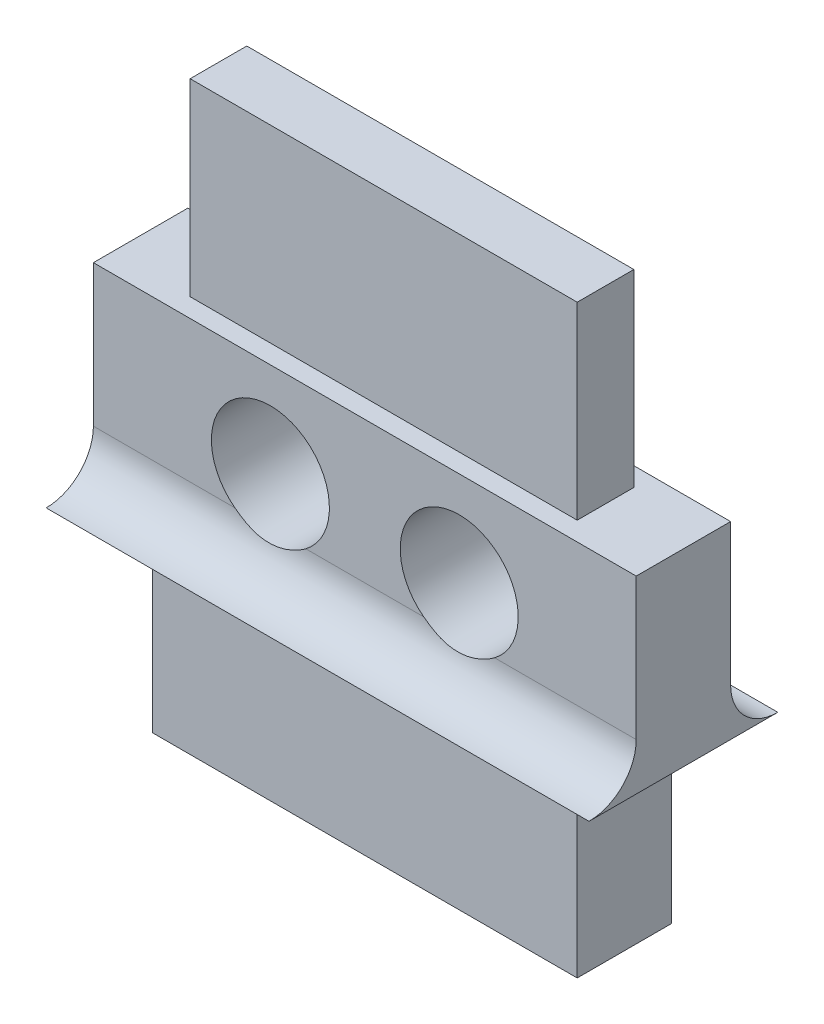
SolidWorks part; units mm, degrees
ref_plane "Front Plane" through (0, 0, 0) normal (0, 0, 1) x (1, 0, 0)
ref_plane "Top Plane" through (0, 0, 0) normal (0, 1, 0) x (1, 0, 0)
ref_plane "Right Plane" through (0, 0, 0) normal (1, 0, 0) x (0, 0, -1)
sketch "Model" plane through (0, 0, 0) normal (0, 0, 1) x (1, 0, 0)
  line L0 (5.7504, 12) -> (5.7504, 0) construction
  line L37 (1.25, 4) -> (0, 4)
  line L38 (10.2507, 4) -> (11.5007, 4)
  line L39 (1.25, 0) -> (10.2507, 0)
  line L40 (1.25, 4) -> (1.25, 0)
  line L41 (10.2507, 4) -> (10.2507, 0)
  line L126 (10.2507, 8) -> (11.5007, 8)
  line L127 (1.25, 8) -> (0, 8)
  line L128 (10.2507, 12) -> (1.25, 12)
  line L129 (10.2507, 8) -> (10.2507, 12)
  line L130 (1.25, 8) -> (1.25, 12)
  line L131 (0, 8) -> (0, 4)
  line L132 (11.5007, 8) -> (11.5007, 4)
  circle A81 centre (7.7507, 6) radius 1.25
  circle A82 centre (3.75, 6) radius 1.25
  dimension "D1" = 2.5
  dimension "D4" = 9.0007
  dimension "D5" = 4
  dimension "D2" = 2
  dimension "D3" = 2.5
  dimension "D6" = 2.5
extrude "Boss-Extrude1" add sketch "Model" along normal blind 2
sketch "Sketch1" plane through (0, 0, 0) normal (-1, 0, 0) x (0, 0, 1)
  line L0 (1, 0) -> (1, 7) construction
  line L1 (2, 4) -> (2, 5)
  line L2 (2, 4) -> (3, 4)
  line L3 (0, 4) -> (-1, 4)
  line L4 (0, 4) -> (0, 5)
  arc A0 (2, 5) -> (3, 4) centre (3, 5) ccw
  arc A1 (0, 5) -> (-1, 4) centre (-1, 5) cw
  dimension "D1" = 1
  dimension "D2" = 1
  dimension "D3" = 4
  dimension "D4" = 1
  dimension "D5" = 2
extrude "Boss-Extrude2" add sketch "Sketch1" against normal up to surface (11.5007 mm away) up to face at (11.5007, 6, 1)
sketch "Sketch2" plane through (0, 0, 2) normal (0, 0, 1) x (1, 0, 0)
  line L0 (5.7504, 12) -> (5.7504, 0) construction
  line L1 (10.2507, 12) -> (1.25, 12) construction
  line L2 (1.25, 0) -> (10.2507, 0) construction
  circle A0 centre (3.75, 6) radius 1.25
  circle A1 centre (7.7507, 6) radius 1.25
  dimension "D1" = 2.5
extrude "Cut-Extrude1" cut sketch "Sketch2" against normal through all both and the other way through all
sketch "Sketch3" plane through (0, 12, 0) normal (0, 1, 0) x (1, 0, 0)
  line L1 (10.2507, 0) -> (1.25, 0)
  line L2 (10.2507, 0) -> (10.2507, -2)
  line L3 (10.2507, -2) -> (1.25, -2)
  line L4 (1.25, 0) -> (1.25, -2)
  line L5 (9.8507, -0.4) -> (1.65, -0.4)
  line L6 (9.8507, -0.4) -> (9.8507, -1.6)
  line L7 (9.8507, -1.6) -> (1.65, -1.6)
  line L8 (1.65, -0.4) -> (1.65, -1.6)
  dimension "D1" = 0.4
  dimension "D2" = 0.4
  dimension "D3" = 0.4
  dimension "D4" = 0.4
extrude "Cut-Extrude2" cut sketch "Sketch3" against normal blind 4
equation "\"D4@Model\"= \"fingerWidth@parametersSketch@prostheticParameters.SLDPRT\" * 0.5556"
equation "\"D2@Sketch3\"=\"tol2@parametersSketch@prostheticParameters.SLDPRT\""
equation "\"D1@Sketch3\"=\"tol2@parametersSketch@prostheticParameters.SLDPRT\""
equation "\"D3@Sketch3\"=\"tol2@parametersSketch@prostheticParameters.SLDPRT\""
equation "\"D4@Sketch3\"=\"tol2@parametersSketch@prostheticParameters.SLDPRT\""
